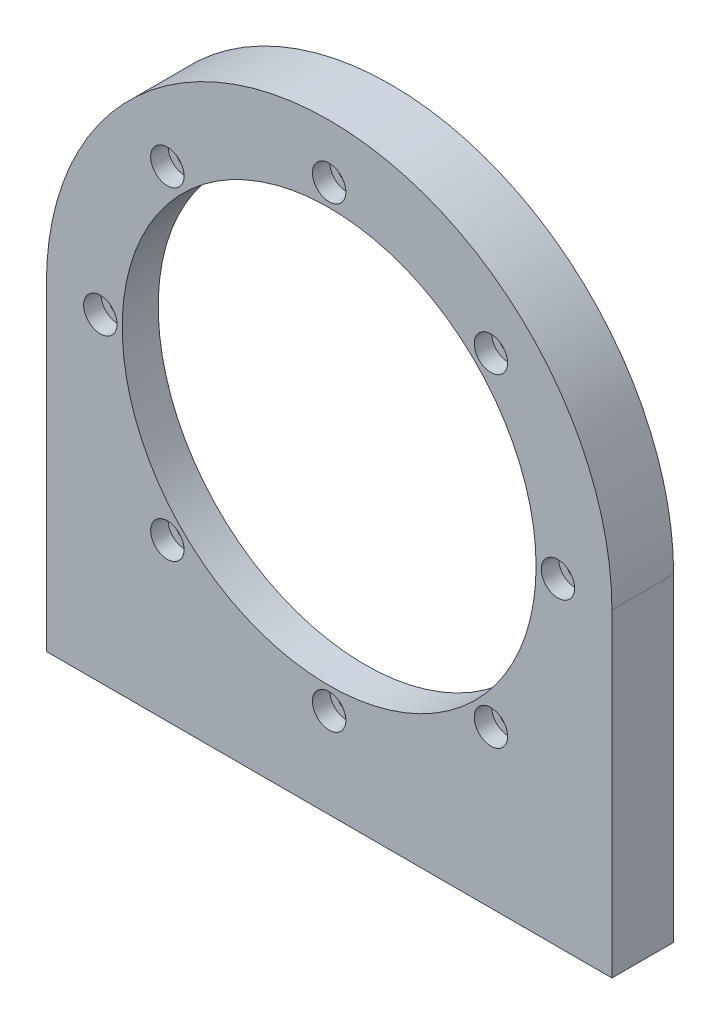
SolidWorks part; units mm, degrees
material "6063-T6"
ref_plane "Front Plane" through (0, 0, 0) normal (0, 0, 1) x (1, 0, 0)
ref_plane "Top Plane" through (0, 0, 0) normal (0, 1, 0) x (1, 0, 0)
ref_plane "Right Plane" through (0, 0, 0) normal (1, 0, 0) x (0, 0, -1)
sketch "Sketch1" plane through (0, 0, 0) normal (0, 0, 1) x (1, 0, 0)
  circle A0 centre (0, 0) radius 55
  circle A1 centre (0, 0) radius 40.25
  dimension "D1" = 110
  dimension "D2" = 80.5
extrude "Boss-Extrude1" add sketch "Sketch1" along normal blind 7
sketch "Sketch2" plane through (0, 0, 7) normal (0, 0, 1) x (1, 0, 0)
  circle A0 centre (0, 0) radius 44.5 construction
  point P5 (0, 44.5)
  point P13 (31.4663, 31.4663)
  point P14 (44.5, 0)
  point P15 (31.4663, -31.4663)
  point P16 (0, -44.5)
  point P17 (-31.4663, -31.4663)
  point P18 (-44.5, 0)
  point P19 (-31.4663, 31.4663)
  dimension "D1" = 89
  dimension "D2" = 8
hole_wizard "CBORE for M3 Hex Socket Head Cap Screw1" positions "Sketch2" profile "Sketch3" counterbore size "M3" standard "DIN" end condition through all
sketch "Sketch3" plane through (-31.4663, 31.4663, 7) normal (1, 0, 0) x (0, -1, 0)
  line L0 (0, 0) -> (0, 7)
  line L1 (0, 7) -> (1.7, 7)
  line L3 (1.7, 7) -> (1.7, 3.4)
  line L4 (1.7, 3.4) -> (3.25, 3.4)
  line L5 (3.25, 3.4) -> (3.25, 0)
  line L7 (3.25, 0) -> (0, 0)
  line L11 (0, -6.35) -> (0, 107.95) construction
  dimension "Thru Hole Dia." = 3.4
  dimension "Thru Hole Depth" = 7
  dimension "C'Bore Dia." = 6.5
  dimension "C'Bore Depth" = 3.4
sketch "Sketch4" plane through (0, 0, 0) normal (0, 0, -1) x (-1, 0, 0)
  circle A0 centre (0, 0) radius 50.3
  circle A1 centre (0, 0) radius 55 construction
  circle A2 centre (0, 0) radius 55
  dimension "D1" = 100.6
extrude "Boss-Extrude3" add sketch "Sketch4" along normal blind 5
sketch "Sketch5" plane through (0, 0, 7) normal (0, 0, 1) x (1, 0, 0)
  line L0 (-55, 0) -> (-55, -62)
  line L1 (-55, -62) -> (55, -62)
  line L2 (55, -62) -> (55, 0)
  circle A0 centre (0, 0) radius 55 construction
  arc A1 (-55, 0) -> (55, 0) centre (0, 0) ccw
  dimension "D1" = 62
extrude "Boss-Extrude4" add sketch "Sketch5" against normal up to surface (12 mm away) up to face at (-55, 0, -5)
sketch "Sketch7" plane through (0, -62, 0) normal (0, -1, 0) x (-1, 0, 0)
  line L0 (-55, -1) -> (55, -1) construction
  line L1 (-55, 5) -> (-55, -7) construction
  line L2 (55, 5) -> (55, -7) construction
  point P9 (0, -1)
  point P19 (25, -1)
  point P20 (50, -1)
  point P21 (0, -1)
  point P22 (25, -1)
  point P23 (-25, -1)
  point P24 (0, -1)
  point P25 (-25, -1)
  point P26 (-50, -1)
  dimension "D1" = 3
  dimension "D2" = 3
hole_wizard "Ø6.4 (6.4) Diameter Hole1" positions "Sketch7" profile "Sketch8" hole size "Ø6.4" standard "BSI"
sketch "Sketch8" plane through (50, -62, 1) normal (1, 0, 0) x (0, 0, -1)
  line L0 (0, 0) -> (0, 11.9228)
  line L1 (0, 11.9228) -> (3.2, 10)
  line L2 (3.2, 10) -> (3.2, 0)
  line L5 (3.2, 0) -> (0, 0)
  line L10 (0, 11.9228) -> (-3.2, 10) construction
  line L11 (0, -6.35) -> (0, 107.95) construction
  dimension "Hole Dia." = 6.4
  dimension "Hole Depth" = 10
  dimension "Drill Angle" = 118
